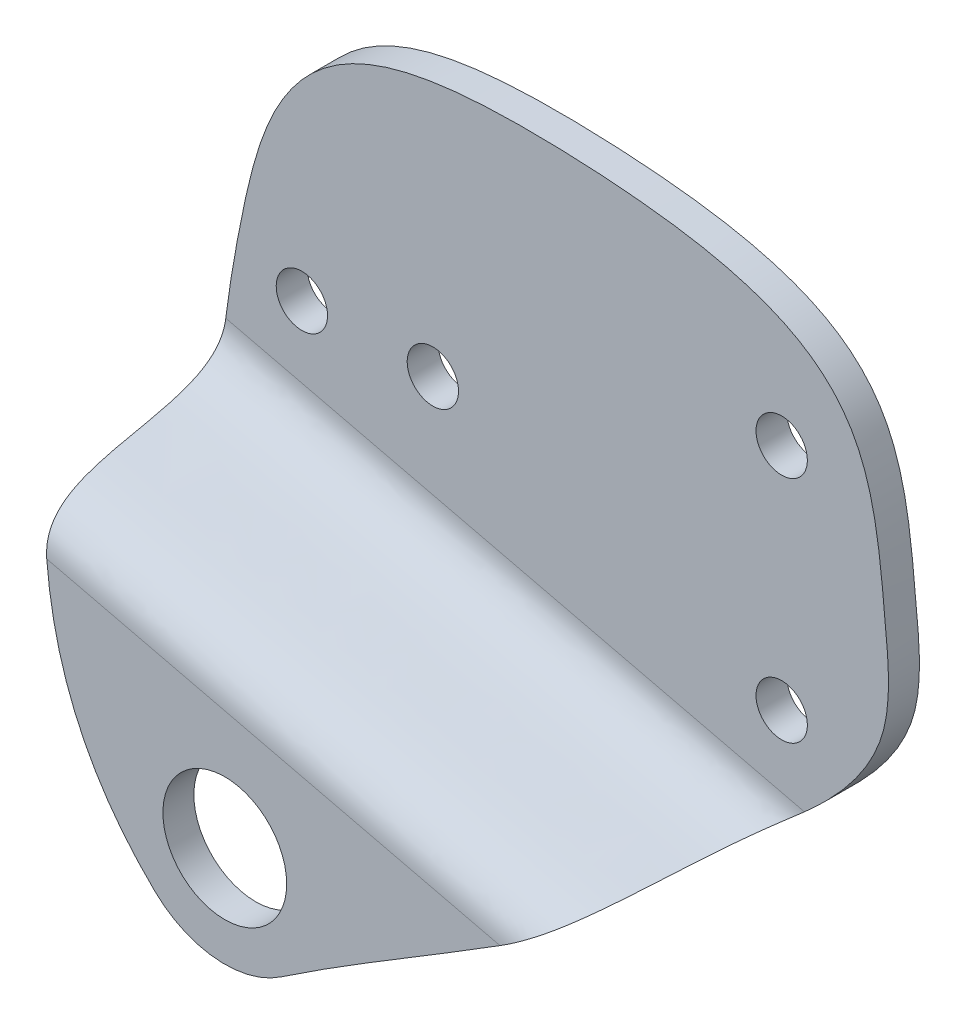
SolidWorks part; units mm, degrees
material "ABS"
ref_plane "Front Plane" through (0, 0, 0) normal (0, 0, 1) x (1, 0, 0)
ref_plane "Top Plane" through (0, 0, 0) normal (0, 1, 0) x (1, 0, 0)
ref_plane "Right Plane" through (0, 0, 0) normal (1, 0, 0) x (0, 0, -1)
sketch "main_features_sketch" plane through (0, 0, 0) normal (0, 0, 1) x (1, 0, 0)
  line L0 (0, -7.3) -> (0, 0) construction
  line L1 (-127, -19.05) -> (127, -19.05) construction
  line L2 (-12.0493, -9.2395) -> (15.4719, -35.7057) construction
  line L3 (-1.2057, -19.8915) -> (-35.1292, -42.8629) construction
  circle A0 centre (-9.525, 25.4) radius 6 construction
  circle A1 centre (3.175, 25.4) radius 6 construction
  circle A2 centre (37, 36.5125) radius 6 construction
  circle A3 centre (37, 14.2875) radius 6 construction
  circle A4 centre (0, -7.3) radius 6
  circle A5 centre (0, -7.3) radius 9.75
  circle A6 centre (-9.525, 25.4) radius 2.4892
  circle A7 centre (3.175, 25.4) radius 2.4892
  circle A8 centre (37, 36.5125) radius 2.4892
  circle A9 centre (37, 14.2875) radius 2.4892
  spline S0 degree 3 poles (-6.7583, -14.3277) (-19.8154, -1.7711) (-17.8681, 18.3746) (-11.5594, 47.1139) (0.7713, 51.6537) (45.1342, 49.0484) (46.0113, 37.2911) (48.8462, 7.8731) (21.9825, -4.1895) (5.4668, -15.3732) knots 0 0 0 0 0.179468 0.221834 0.401236 0.45577 0.712637 0.770271 1 1 1 1
  dimension "D1" = 12
  dimension "D2" = 19.5
  dimension "D4" = 12
  dimension "D5" = 4.9784
  dimension "D3" = 2
extrude "Boss-Extrude1" add sketch "main_features_sketch" along normal blind 20 contours S0 A5 A9 A8 A7 A6 | A5 A4 region at (8.3693, -11.7403, 0) region at (14.0249, 22.7845, 0)
ref_plane "Plane1" through (4.647, 19.4558, 0) normal (0.2323, 0.9726, 0) x (0.9726, -0.2323, 0)
ref_plane "cut_plane" through (-12.3292, 2.9448, 0) normal (-0.9726, 0.2323, 0) x (0, 0, 1)
sketch "Sketch2" plane through (-12.676, 1.4928, 0) normal (0.9726, -0.2323, 0) x (0, 0, -1)
  line L0 (-3, 56.3464) -> (-3, 17.2679)
  line L1 (-20, -15.3574) -> (-20, 5.6129)
  line L3 (0, -14.0129) -> (0, 56.3464) construction
  line L4 (-20, 2.5676) -> (-20, 15.7103) construction
  line L5 (-3, 22.2829) -> (-3, 34.5715) construction
  line L6 (0, 56.3464) -> (0, 15.4609)
  line L7 (-17, 4.54) -> (-17, -15.3574)
  line L8 (-20, -15.3574) -> (0, -15.3574) construction
  line L9 (0, 56.3464) -> (-20, 56.3464) construction
  line L10 (-3, 56.3464) -> (0, 56.3464)
  line L11 (-17, -15.3574) -> (-20, -15.3574)
  line L12 (-17, 0.1846) -> (-17, 6.182) construction
  line L13 (0, 2.2857) -> (0, 6.7648) construction
  line L14 (0, 15.4609) -> (0, -15.3574)
  line L15 (0, -15.3574) -> (-17, -15.3574)
  line L16 (-20, 5.6129) -> (-20, 56.3464)
  line L17 (-20, 56.3464) -> (-3, 56.3464)
  spline S0 degree 3 poles (-3, 17.2679) (-3, 9.5875) (-20, 13.8271) (-20, 5.6129) knots 0 0 0 0 1 1 1 1
  spline S1 degree 3 poles (0, 15.4609) (0, 9.0167) (-17, 7.0389) (-17, 4.54) knots 0 0 0 0 1 1 1 1
  dimension "D2" = 3
extrude "Cut-Extrude1" cut sketch "Sketch2" against normal through all both and the other way through all contours L0 S0 L16 L17 | S1 L14 L15 L7 region at (-4.7924, 34.4994, 11.6965) region at (-13.4102, -1.581, 8.0397)
